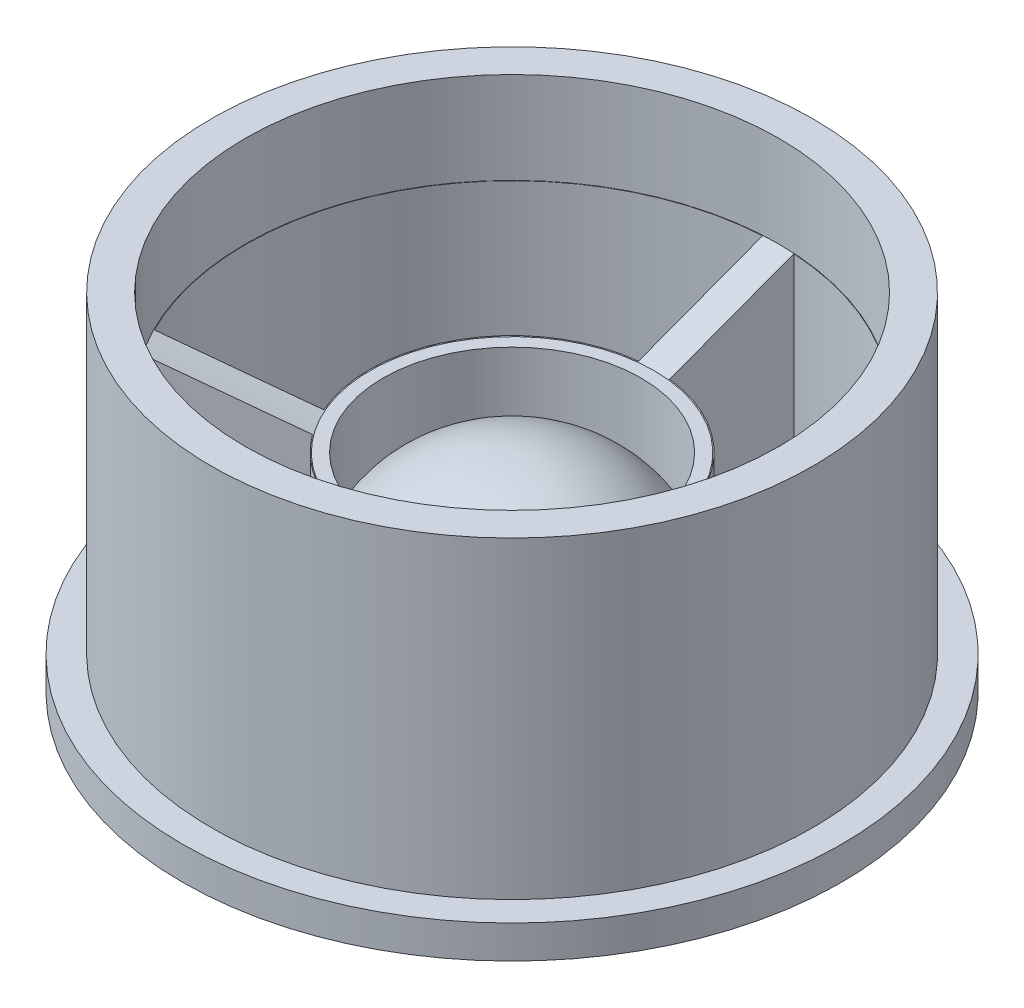
SolidWorks part; units mm, degrees
ref_plane "前视基准面" through (0, 0, 0) normal (0, 0, 1) x (1, 0, 0)
ref_plane "上视基准面" through (0, 0, 0) normal (0, 1, 0) x (1, 0, 0)
ref_plane "右视基准面" through (0, 0, 0) normal (1, 0, 0) x (0, 0, -1)
sketch "草图1" plane through (0, 0, 0) normal (0, 1, 0) x (1, 0, 0)
  line L0 (0.4731, 8.0758) -> (0.4731, 4.3078)
  line L1 (0, -2.7698) -> (0, 1.1) construction
  line L2 (-0.4731, 8.0758) -> (-0.4731, 4.3078)
  line L3 (6.7573, -4.4476) -> (3.4941, -2.5636)
  line L4 (0, 4.3337) -> (0, 8.0896) construction
  line L5 (7.2304, -3.6281) -> (3.9672, -1.7441)
  line L6 (-7.2304, -3.6281) -> (-3.9672, -1.7441)
  line L7 (-6.7573, -4.4476) -> (-3.4941, -2.5636)
  line L8 (0, 9.1283) -> (0, 11.8114) construction
  circle A0 centre (0, 0) radius 1.1
  circle A2 centre (0, 0) radius 10
  circle A3 centre (0, 0) radius 3.4997
  circle A4 centre (0, 0) radius 4.3337
  circle A5 centre (0, 0) radius 9.1283
  circle A6 centre (0, 0) radius 8.0896
  point P25 (0, 0)
  dimension "D1" = 3
  dimension "D2" = 20
extrude "凸台-拉伸2" add sketch "草图1" along normal blind 1 contours A2 | A2 A5 region at (-9.7172, 0, 0)
extrude "凸台-拉伸4" add sketch "草图1<4>" along normal blind 10.5 contours A5 | A4 A3 | A4 L6 L7 | A4 L0 L2 | A4 L3 L5 | A3 A0 | A0 region at (0, 0, -6.205) region at (3.1361, 0, -2.8105) region at (5.3737, 0, 3.1025) region at (-5.3737, 0, 3.1025) region at (0, 0, 0) region at (-3.4008, 0, 0) region at (-8.8702, 0, 0)
sketch "草图1<4>" plane through (0, 0, 0) normal (0, 1, 0) x (1, 0, 0) same geometry as "草图1"
sketch "草图2" plane through (0, 0, 0) normal (1, 0, 0) x (0, 0, -1)
  line L0 (0, 2.7027) -> (0, 11.4758) construction
  line L1 (8.099, 10.5) -> (8.099, 7.719)
  line L3 (8.099, 7.719) -> (4.3078, 6.2934)
  line L4 (4.3078, 10.5) -> (4.3078, 0) construction
  line L5 (4.3078, 6.2934) -> (3.9167, 6.2934)
  line L6 (0, 6.2934) -> (0, 10.5)
  line L7 (9.1283, 10.5) -> (-9.1283, 10.5) construction
  line L8 (0, 10.5) -> (8.099, 10.5)
  line L9 (3.9167, 6.2934) -> (3.9167, 3.9641)
  line L11 (0, 6.1717) -> (0, 6.2934)
  spline S0 degree 3 poles (3.9167, 3.9641) (3.1985, 5.3669) (1.5563, 6.233) (0, 6.1717) knots 0 0 0 0 1 1 1 1
revolve "切除-旋转1" cut sketch "草图2" angle 360 about L0
extrude "切除-拉伸1" cut sketch "草图1<5>" along normal blind 5 contours A0 region at (0, 0, 0)
sketch "草图1<5>" plane through (0, 0, 0) normal (0, 1, 0) x (1, 0, 0) same geometry as "草图1"
sketch "草图3" plane through (0, 0, 0) normal (1, 0, 0) x (0, 0, -1)
  line L0 (1.1, 0) -> (1.1, -4)
  line L1 (1.1, -4) -> (1.8586, -4)
  line L3 (4.2749, 0) -> (1.1, 0)
  spline S0 degree 2 poles (1.8586, -4) (1.9706, -1.4578) (4.2749, 0) knots 0 0 0 1 1 1
  dimension "D1" = 4
ref_axis "基准轴1" through (0, -4.725, 0) along (0, 1, 0)
revolve "旋转1" add sketch "草图3" angle 360 about axis through (0, -4.725, 0) along (0, 1, 0)
